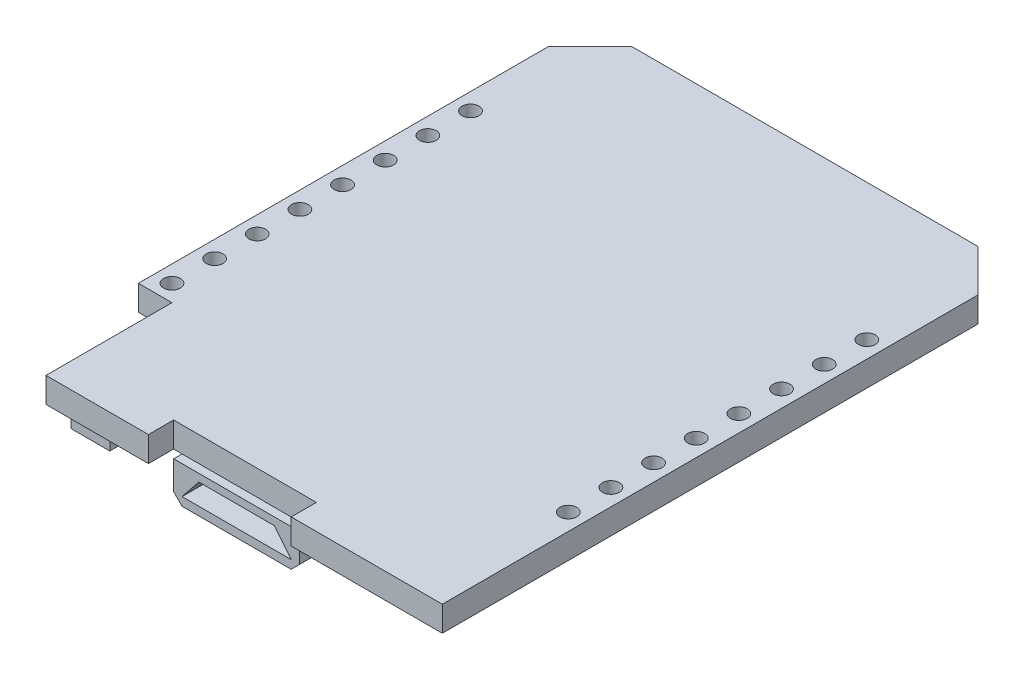
SolidWorks part; units mm, degrees
note: The reader was unsure of these and kept them because the rebuilt part matched: shared geometry of "Sketch5<4>", "Sketch5<5>", "Sketch5<6>".
other "PCB"
other "USB Micro"
ref_plane "Front Plane" through (0, 0, 0) normal (0, 0, 1) x (1, 0, 0)
ref_plane "Top Plane" through (0, 0, 0) normal (0, 1, 0) x (1, 0, 0)
ref_plane "Right Plane" through (0, 0, 0) normal (1, 0, 0) x (0, 0, -1)
sketch "Sketch1" plane through (0, 0, 0) normal (0, 1, 0) x (1, 0, 0)
  line L0 (0, 0) -> (0, 31.9)
  line L1 (0, 31.9) -> (-2.5, 34.4)
  line L2 (-2.5, 34.4) -> (-23.1, 34.4)
  line L3 (-23.1, 34.4) -> (-25.6, 31.9)
  line L4 (-25.6, 31.9) -> (-25.6, 7.5)
  line L5 (-25.6, 7.5) -> (-23.6, 7.5)
  line L6 (-23.6, 7.5) -> (-23.6, 0)
  line L7 (0, 0) -> (-9, 0)
  line L8 (-9, 0) -> (-9, 1.5)
  line L9 (-9, 1.5) -> (-17.5, 1.5)
  line L10 (-17.5, 1.5) -> (-17.5, 0)
  line L11 (-17.5, 0) -> (-23.6, 0)
  line L12 (-1, -1.7092) -> (-1, 37.7939) construction
  line L13 (-24.6, 37.7939) -> (-24.6, -1.7092) construction
  line L14 (-28.0763, 8.5) -> (2.6406, 8.5) construction
  circle A0 centre (-24.6, 8.5) radius 0.5
  circle A1 centre (-1, 8.5) radius 0.5
  circle A2 centre (-24.6, 11.04) radius 0.5
  circle A3 centre (-1, 11.04) radius 0.5
  circle A4 centre (-24.6, 13.58) radius 0.5
  circle A5 centre (-1, 13.58) radius 0.5
  circle A6 centre (-24.6, 16.12) radius 0.5
  circle A7 centre (-1, 16.12) radius 0.5
  circle A8 centre (-24.6, 18.66) radius 0.5
  circle A9 centre (-1, 18.66) radius 0.5
  circle A10 centre (-24.6, 21.2) radius 0.5
  circle A11 centre (-1, 21.2) radius 0.5
  circle A12 centre (-24.6, 23.74) radius 0.5
  circle A13 centre (-1, 23.74) radius 0.5
  circle A14 centre (-24.6, 26.28) radius 0.5
  circle A15 centre (-1, 26.28) radius 0.5
  dimension "D13" = 1
  dimension "D1" = 25.6
  dimension "D2" = 34.4
  dimension "D3" = 2.5
  dimension "D4" = 2.5
  dimension "D5" = 7.5
  dimension "D6" = 2
  dimension "D7" = 8.5
  dimension "D8" = 1.5
  dimension "D9" = 9
  dimension "D10" = 1
  dimension "D11" = 1
  dimension "D12" = 8.5
  dimension "D14" = 8
extrude "PCB" add sketch "Sketch1" along normal blind 1.5
sketch "Sketch2" plane through (0, 1.5, 0) normal (0, 1, 0) x (1, 0, 0)
  line L0 (-2.5, 34.4) -> (-23.1, 34.4) construction
  line L1 (-20.8, 34.4) -> (-4.8, 34.4)
  line L2 (-20.8, 34.4) -> (-20.8, 10.4)
  line L3 (-20.8, 10.4) -> (-4.8, 10.4)
  line L4 (-4.8, 34.4) -> (-4.8, 10.4)
  point P6 (-12.8, 34.4)
  point P7 (-12.8, 34.4)
  point P8 (-12.8, 34.4)
  point P9 (-12.8, 34.4)
  point P10 (-12.8, 34.4)
  point P11 (-12.8, 34.4)
  point P12 (-4.8, 31.3326)
  dimension "D1" = 24
  dimension "D2" = 16
sketch "Sketch5" plane through (0, 0, 0) normal (0, -1, 0) x (1, 0, 0)
  line L0 (-23.6, -7.5) -> (-23.6, 0) construction
  line L1 (-23.6, -1.5) -> (-21.3, -1.5)
  line L2 (-23.6, -1.5) -> (-23.6, -6)
  line L3 (-23.6, -6) -> (-21.3, -6)
  line L4 (-21.3, -1.5) -> (-21.3, -6)
  line L5 (-3.9144, -3.7056) -> (-2.4144, -3.7056)
  line L6 (-17, -1) -> (-9.5, -1)
  line L7 (-17, -1) -> (-17, -6.6)
  line L8 (-17, -6.6) -> (-9.5, -6.6)
  line L9 (-9.5, -1) -> (-9.5, -6.6)
  line L10 (-3.9144, -3.7056) -> (-3.9144, -2.7056)
  line L11 (-18.7643, -9.825) -> (-8.6486, -9.825)
  line L12 (-18.7643, -9.825) -> (-18.7643, -14.4)
  line L13 (-18.7643, -14.4) -> (-8.6486, -14.4)
  line L14 (-8.6486, -9.825) -> (-8.6486, -14.4)
  line L15 (-2.5, -34.4) -> (-23.1, -34.4) construction
  line L16 (-20.1, -28.4) -> (-18.6, -28.4)
  line L17 (-20.1, -28.4) -> (-20.1, -27.4)
  line L18 (-20.1, -27.4) -> (-18.6, -27.4)
  line L19 (-3.9144, -2.7056) -> (-2.4144, -2.7056)
  line L20 (-2.4144, -3.7056) -> (-2.4144, -2.7056)
  line L21 (-6.0768, -10.9216) -> (-6.0768, -9.4216)
  line L22 (-6.0768, -10.9216) -> (-7.0768, -10.9216)
  line L23 (-7.0768, -10.9216) -> (-7.0768, -9.4216)
  line L24 (-6.0768, -9.4216) -> (-7.0768, -9.4216)
  line L25 (-4.477, -10.9216) -> (-4.477, -9.4216)
  line L26 (-4.477, -10.9216) -> (-5.477, -10.9216)
  line L27 (-5.477, -10.9216) -> (-5.477, -9.4216)
  line L28 (-4.477, -9.4216) -> (-5.477, -9.4216)
  line L29 (-7.3592, -3.3369) -> (-7.3592, -1.8369)
  line L30 (-7.3592, -3.3369) -> (-8.3592, -3.3369)
  line L31 (-17.5, -1.5) -> (-9, -1.5) construction
  line L32 (-18.6, -28.4) -> (-18.6, -27.4)
  line L33 (-25.6, -31.9) -> (-25.6, -7.5) construction
  line L34 (-13.6, -28.4) -> (-12.1, -28.4)
  line L35 (-13.6, -28.4) -> (-13.6, -27.4)
  line L36 (-13.6, -27.4) -> (-12.1, -27.4)
  line L37 (-12.1, -28.4) -> (-12.1, -27.4)
  line L38 (-7.1, -28.4) -> (-5.6, -28.4)
  line L39 (-7.1, -28.4) -> (-7.1, -27.4)
  line L40 (-7.1, -27.4) -> (-5.6, -27.4)
  line L41 (-5.6, -28.4) -> (-5.6, -27.4)
  line L42 (-13.6, -26.4) -> (-12.1, -26.4) [skipped]
  line L43 (-13.6, -26.4) -> (-13.6, -25.4) [skipped]
  line L44 (-13.6, -25.4) -> (-12.1, -25.4) [skipped]
  line L45 (-12.1, -26.4) -> (-12.1, -25.4) [skipped]
  line L46 (-7.1, -26.4) -> (-5.6, -26.4)
  line L47 (-7.1, -26.4) -> (-7.1, -25.4)
  line L48 (-7.1, -25.4) -> (-5.6, -25.4)
  line L49 (-5.6, -26.4) -> (-5.6, -25.4)
  line L50 (-13.6, -24.4) -> (-12.1, -24.4)
  line L51 (-13.6, -24.4) -> (-13.6, -23.4)
  line L52 (-13.6, -23.4) -> (-12.1, -23.4)
  line L53 (-12.1, -24.4) -> (-12.1, -23.4)
  line L54 (-7.1, -24.4) -> (-5.6, -24.4) [skipped]
  line L55 (-7.1, -24.4) -> (-7.1, -23.4) [skipped]
  line L56 (-7.1, -23.4) -> (-5.6, -23.4) [skipped]
  line L57 (-5.6, -24.4) -> (-5.6, -23.4) [skipped]
  line L58 (-13.6, -22.4) -> (-12.1, -22.4)
  line L59 (-13.6, -22.4) -> (-13.6, -21.4)
  line L60 (-13.6, -21.4) -> (-12.1, -21.4)
  line L61 (-12.1, -22.4) -> (-12.1, -21.4)
  line L62 (-7.1, -22.4) -> (-5.6, -22.4) [skipped]
  line L63 (-7.1, -22.4) -> (-7.1, -21.4) [skipped]
  line L64 (-7.1, -21.4) -> (-5.6, -21.4) [skipped]
  line L65 (-5.6, -22.4) -> (-5.6, -21.4) [skipped]
  line L66 (-13.6, -20.4) -> (-12.1, -20.4) [skipped]
  line L67 (-13.6, -20.4) -> (-13.6, -19.4) [skipped]
  line L68 (-13.6, -19.4) -> (-12.1, -19.4) [skipped]
  line L69 (-12.1, -20.4) -> (-12.1, -19.4) [skipped]
  line L70 (-7.1, -20.4) -> (-5.6, -20.4)
  line L71 (-7.1, -20.4) -> (-7.1, -19.4)
  line L72 (-7.1, -19.4) -> (-5.6, -19.4)
  line L73 (-5.6, -20.4) -> (-5.6, -19.4)
  line L74 (-13.6, -18.4) -> (-12.1, -18.4)
  line L75 (-13.6, -18.4) -> (-13.6, -17.4)
  line L76 (-13.6, -17.4) -> (-12.1, -17.4)
  line L77 (-12.1, -18.4) -> (-12.1, -17.4)
  line L78 (-7.1, -18.4) -> (-5.6, -18.4)
  line L79 (-7.1, -18.4) -> (-7.1, -17.4)
  line L80 (-7.1, -17.4) -> (-5.6, -17.4)
  line L81 (-5.6, -18.4) -> (-5.6, -17.4)
  line L82 (-13.6, -16.4) -> (-12.1, -16.4) [skipped]
  line L83 (-13.6, -16.4) -> (-13.6, -15.4) [skipped]
  line L84 (-13.6, -15.4) -> (-12.1, -15.4) [skipped]
  line L85 (-12.1, -16.4) -> (-12.1, -15.4) [skipped]
  line L86 (-7.1, -16.4) -> (-5.6, -16.4)
  line L87 (-7.1, -16.4) -> (-7.1, -15.4)
  line L88 (-7.1, -15.4) -> (-5.6, -15.4)
  line L89 (-5.6, -16.4) -> (-5.6, -15.4)
  line L90 (-13.6, -14.4) -> (-12.1, -14.4) [skipped]
  line L91 (-13.6, -14.4) -> (-13.6, -13.4) [skipped]
  line L92 (-13.6, -13.4) -> (-12.1, -13.4) [skipped]
  line L93 (-12.1, -14.4) -> (-12.1, -13.4) [skipped]
  line L94 (-7.1, -14.4) -> (-5.6, -14.4)
  line L95 (-7.1, -14.4) -> (-7.1, -13.4)
  line L96 (-7.1, -13.4) -> (-5.6, -13.4)
  line L97 (-5.6, -14.4) -> (-5.6, -13.4)
  line L98 (-20.1, -26.4) -> (-18.6, -26.4)
  line L99 (-20.1, -26.4) -> (-20.1, -25.4)
  line L100 (-20.1, -25.4) -> (-18.6, -25.4)
  line L101 (-18.6, -26.4) -> (-18.6, -25.4)
  line L102 (-20.1, -24.4) -> (-18.6, -24.4)
  line L103 (-20.1, -24.4) -> (-20.1, -23.4)
  line L104 (-20.1, -23.4) -> (-18.6, -23.4)
  line L105 (-18.6, -24.4) -> (-18.6, -23.4)
  line L106 (-20.1, -22.4) -> (-18.6, -22.4)
  line L107 (-20.1, -22.4) -> (-20.1, -21.4)
  line L108 (-20.1, -21.4) -> (-18.6, -21.4)
  line L109 (-18.6, -22.4) -> (-18.6, -21.4)
  line L110 (-20.1, -20.4) -> (-18.6, -20.4)
  line L111 (-20.1, -20.4) -> (-20.1, -19.4)
  line L112 (-20.1, -19.4) -> (-18.6, -19.4)
  line L113 (-18.6, -20.4) -> (-18.6, -19.4)
  line L114 (-20.1, -18.4) -> (-18.6, -18.4)
  line L115 (-20.1, -18.4) -> (-20.1, -17.4)
  line L116 (-20.1, -17.4) -> (-18.6, -17.4)
  line L117 (-18.6, -18.4) -> (-18.6, -17.4)
  line L118 (-20.1, -16.4) -> (-18.6, -16.4)
  line L119 (-20.1, -16.4) -> (-20.1, -15.4)
  line L120 (-20.1, -15.4) -> (-18.6, -15.4)
  line L121 (-18.6, -16.4) -> (-18.6, -15.4)
  line L122 (-20.1, -14.4) -> (-18.6, -14.4) [skipped]
  line L123 (-20.1, -14.4) -> (-20.1, -13.4) [skipped]
  line L124 (-20.1, -13.4) -> (-18.6, -13.4) [skipped]
  line L125 (-18.6, -14.4) -> (-18.6, -13.4) [skipped]
  line L126 (-23.6, 0) -> (-17.5, 0) construction
  line L127 (-8.3592, -3.3369) -> (-8.3592, -1.8369)
  line L128 (-7.3592, -1.8369) -> (-8.3592, -1.8369)
  line L129 (-5.4144, -1.8369) -> (-3.9144, -1.8369)
  line L130 (-5.4144, -1.8369) -> (-5.4144, -0.8369)
  line L131 (-5.4144, -0.8369) -> (-3.9144, -0.8369)
  line L132 (-3.9144, -1.8369) -> (-3.9144, -0.8369)
  line L133 (-7.2524, -7.3947) -> (-7.2524, -5.8947)
  line L134 (-7.2524, -7.3947) -> (-8.2524, -7.3947)
  line L135 (-8.2524, -7.3947) -> (-8.2524, -5.8947)
  line L136 (-7.2524, -5.8947) -> (-8.2524, -5.8947)
  line L137 (-4.3695, -7.2325) -> (-2.8695, -7.2325)
  line L138 (-4.3695, -7.2325) -> (-4.3695, -6.2325)
  line L139 (-4.3695, -6.2325) -> (-2.8695, -6.2325)
  line L140 (-2.8695, -7.2325) -> (-2.8695, -6.2325)
  line L141 (-18.357, -8.0394) -> (-18.357, -5.3089)
  line L142 (-18.357, -8.0394) -> (-19.357, -8.0394)
  line L143 (-19.357, -8.0394) -> (-19.357, -5.3089)
  line L144 (-18.357, -5.3089) -> (-19.357, -5.3089)
  line L145 (-9, 0) -> (0, 0) construction
  line L146 (-20.1, -28.4) -> (-13.6, -28.4) construction
  line L147 (-20.1, -28.4) -> (-20.1, -26.4) construction
  point P38 (-13.25, -1.5)
  point P131 (-13.25, -1)
  point P132 (-13.25, -1.5)
  dimension "D1" = 1.5
  dimension "D2" = 1
  dimension "D3" = 6
  dimension "D4" = 5.5
  dimension "D6" = 2.3
  dimension "D7" = 4.5
  dimension "D8" = 1.5
  dimension "D9" = 8
  dimension "D10" = 7.5
  dimension "D11" = 5.6
  dimension "D12" = 90
  dimension "D13" = 6.5
  dimension "D14" = 2
  dimension "D5" = 3
extrude "Boss-Extrude4" add sketch "Sketch5" along normal blind 2.2 separate body contours L7 L8 L9 L6
chamfer "Chamfer1" distance 0.5 angle 45 2 edges at (-9.5, -2.2, -3.8) (-17, -2.2, -3.8)
sketch "Sketch12" plane through (0, 0, -1) normal (0, 0, 1) x (1, 0, 0)
  line L0 (-15.5, -0.45) -> (-11, -0.45)
  line L1 (-11, -0.45) -> (-10, -1.7)
  line L2 (-10, -1.7) -> (-16.5, -1.7)
  line L3 (-16.5, -1.7) -> (-15.5, -0.45)
  line L4 (-17, 0) -> (-9.5, 0) construction
  line L5 (-16.5, -2.2) -> (-10, -2.2) construction
  line L6 (-9.5, -1.7) -> (-9.5, 0) construction
  point P2 (-13.25, -0.45)
  point P5 (-13.25, 0)
  point P6 (-13.25, -1.7)
  point P9 (-13.25, -2.2)
  dimension "D1" = 0.5
  dimension "D2" = 1.5
  dimension "D3" = 0.5
  dimension "D4" = 1.75
extrude "Cut-Extrude1" cut sketch "Sketch12" against normal blind 4 from surface at 0 starting at face at (-13.25, -1.3, -1)
extrude "Button Body" add sketch "Sketch5<4>" along normal blind 2 from surface at 0 separate body starting at face at (-24.6, 0, -25.78)
sketch "Sketch5<4>" plane through (0, 0, 0) normal (0, -1, 0) x (1, 0, 0) same geometry as "Sketch5"
sketch "Sketch11" plane through (-23.6, 0, 0) normal (-1, 0, 0) x (0, 0, 1)
  line L0 (-6, -2) -> (-1.5, 0) construction
  line L1 (-6, 0) -> (-1.5, -2) construction
  line L2 (-7.5, 0) -> (0, 0) construction
  line L3 (-4.75, -1.4475) -> (-2.75, -1.4475)
  line L4 (-4.75, -1.4475) -> (-4.75, -0.5525)
  line L5 (-4.75, -0.5525) -> (-2.75, -0.5525)
  line L6 (-2.75, -1.4475) -> (-2.75, -0.5525)
  line L7 (-4.75, -1.4475) -> (-2.75, -0.5525) construction
  line L8 (-4.75, -0.5525) -> (-2.75, -1.4475) construction
  line L9 (-6, 0) -> (-1.5, 0) construction
  point P8 (-3.75, -1)
  point P9 (-3.75, -1)
  dimension "D1" = 2
  dimension "D2" = 0.5525
  dimension "D3" = 1.25
  dimension "D4" = 1
  dimension "D5" = 2
extrude "Button Actuator" add sketch "Sketch11" along normal blind 1 separate body
extrude "Components1" add sketch "Sketch5<5>" along normal blind 1 from surface at 0 separate body contours L5 L20 L19 L10 | L14 L11 L12 L13 | L34 L37 L36 L35 | L74 L77 L76 L75 | L29 L128 L127 L30 starting at face at (-24.6, 0, -25.78)
sketch "Sketch5<5>" plane through (0, 0, 0) normal (0, -1, 0) x (1, 0, 0) same geometry as "Sketch5"
extrude "Components 2" add sketch "Sketch5<6>" along normal blind 0.5 from surface at 0 separate body contours L118 L121 L120 L119 | L114 L117 L116 L115 | L110 L113 L112 L111 | L106 L109 L108 L107 | L102 L105 L104 L103 | L98 L101 L100 L99 | L16 L32 L18 L17 | L50 L53 L52 L51 | L58 L61 L60 L59 | L141 L144 L143 L142 | L129 L132 L131 L130 | L133 L136 L135 L134 | L137 L140 L139 L138 | L25 L28 L27 L26 | L21 L24 L23 L22 | L94 L97 L96 L95 | L86 L89 L88 L87 | L78 L81 L80 L79 | L70 L73 L72 L71 | L46 L49 L48 L47 | L38 L41 L40 L39 starting at face at (-24.6, 0, -25.78)
sketch "Sketch5<6>" plane through (0, 0, 0) normal (0, -1, 0) x (1, 0, 0) same geometry as "Sketch5"
sketch "Sketch13" plane through (0, 0, 0) normal (0, -1, 0) x (-1, 0, 0)
  line L0 (12.8, 38.7908) -> (12.8, -3.1035) construction
  line L1 (2.5, 34.4) -> (23.1, 34.4) construction
  point P3 (12.8, 34.4)
